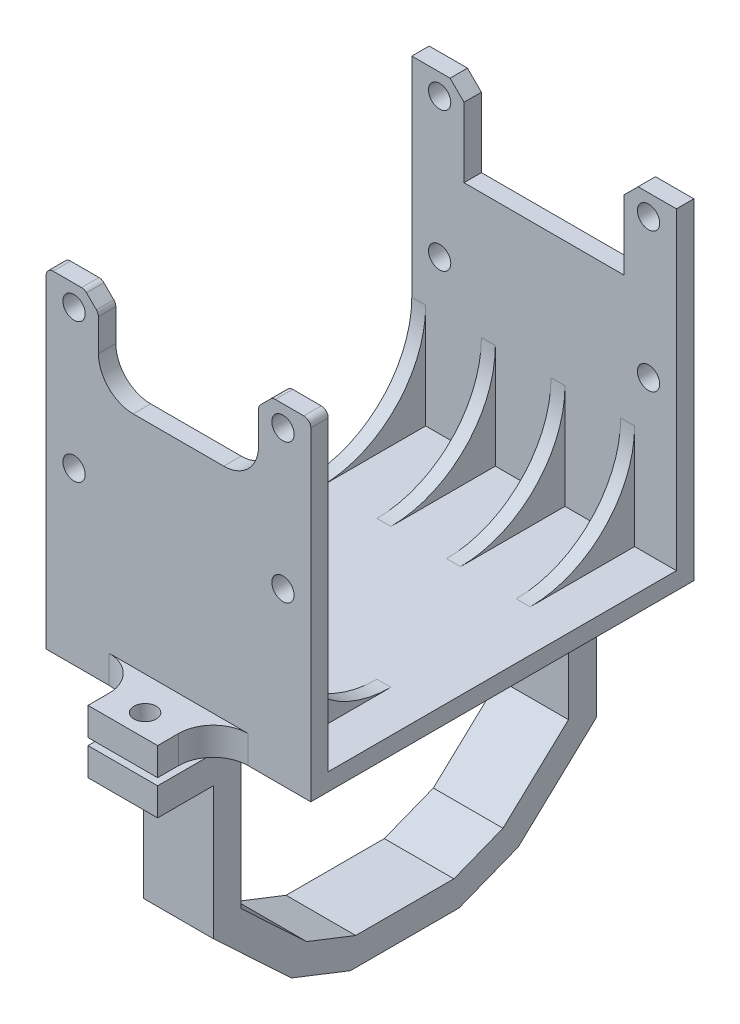
SolidWorks part; units mm, degrees
ref_plane "前视基准面" through (0, 0, 0) normal (0, 0, 1) x (1, 0, 0)
ref_plane "上视基准面" through (0, 0, 0) normal (0, 1, 0) x (1, 0, 0)
ref_plane "右视基准面" through (0, 0, 0) normal (1, 0, 0) x (0, 0, -1)
sketch "草图1" plane through (0, 0, 0) normal (0, 0, 1) x (1, 0, 0)
  line L1 (-19.3201, 24.1356) -> (18.6799, 24.1356)
  line L2 (-19.3201, 24.1356) -> (-19.3201, -20.8644)
  line L3 (-19.3201, -20.8644) -> (18.6799, -20.8644)
  line L4 (18.6799, 24.1356) -> (18.6799, -20.8644)
  circle A0 centre (-15.3201, 21.1356) radius 1.6
  circle A1 centre (14.6799, 21.1356) radius 1.6
  circle A2 centre (-15.3201, 1.1356) radius 1.6
  circle A3 centre (14.6799, 1.1356) radius 1.6
  dimension "D3" = 30
  dimension "D4" = 30
  dimension "D5" = 20
  dimension "D6" = 3.2
  dimension "D7" = 3.2
  dimension "D8" = 3.2
  dimension "D9" = 3.2
  dimension "D10" = 4
  dimension "D11" = 4
  dimension "D12" = 3
  dimension "D13" = 3
  dimension "D1" = 38
  dimension "D2" = 45
extrude "凸台-拉伸1" add sketch "草图1" along normal blind 2.5
sketch "草图2" plane through (0, 0, 2.5) normal (0, 0, 1) x (1, 0, 0)
  line L0 (18.6799, 24.1356) -> (-19.3201, 24.1356) construction
  line L1 (-11.8201, 24.1356) -> (11.1799, 24.1356)
  line L2 (-11.8201, 22.1356) -> (-11.8201, 12.1356)
  line L3 (-11.8201, 12.1356) -> (11.1799, 12.1356)
  line L4 (11.1799, 22.1356) -> (11.1799, 12.1356)
  line L5 (-13.8201, 24.1356) -> (-11.8201, 22.1356)
  line L6 (-11.8201, 24.1356) -> (-13.8201, 24.1356)
  line L7 (11.1799, 22.1356) -> (13.1799, 24.1356)
  line L8 (13.1799, 24.1356) -> (11.1799, 24.1356)
  circle A0 centre (-15.3201, 21.1356) radius 1.6 construction
  circle A1 centre (14.6799, 21.1356) radius 1.6 construction
  dimension "D2" = 3.5
  dimension "D1" = 3.5
  dimension "D3" = 12
  dimension "D4" = 2
  dimension "D5" = 2
  dimension "D6" = 2
  dimension "D7" = 2
extrude "切除-拉伸1" cut sketch "草图2" against normal blind 2.5
sketch "草图3" plane through (0, -20.8644, 0) normal (0, -1, 0) x (1, 0, 0)
  line L0 (18.6799, 2.5) -> (18.6799, 0) construction
  line L1 (-19.3201, 2.5) -> (18.6799, 2.5)
  line L2 (-19.3201, 2.5) -> (-19.3201, -52.5)
  line L3 (-19.3201, -52.5) -> (18.6799, -52.5)
  line L4 (18.6799, 2.5) -> (18.6799, -52.5)
  dimension "D1" = 55
extrude "凸台-拉伸2" add sketch "草图3" along normal blind 2.5
fillet "圆角3" radius 1 6 edges at (11.1799, 22.1356, 1.25) (13.1799, 24.1356, 1.25) (-19.3201, 24.1356, 1.25) (18.6799, 24.1356, 1.25) (-11.8201, 22.1356, 1.25) (-13.8201, 24.1356, 1.25)
fillet "Fillet1" radius 5 2 edges at (-11.8201, 12.1356, 1.25) (11.1799, 12.1356, 1.25)
sketch "Sketch4" plane through (-19.3201, 0, 0) normal (-1, 0, 0) x (0, 0, 1)
  line L0 (0, -5.8644) -> (0, -20.8644)
  line L1 (0, 23.1356) -> (0, -20.8644) construction
  line L2 (0, -20.8644) -> (-15, -20.8644)
  line L3 (0, -20.8644) -> (-52.5, -20.8644) construction
  arc A0 (0, -5.8644) -> (-15, -20.8644) centre (-15, -5.8644) cw
  dimension "D1" = 15
extrude "Extrude3" add sketch "Sketch4" against normal blind 2
ref_plane "Plane1" through (0, 0, -25) normal (0, 0, -1) x (-1, 0, 0)
mirror "Mirror1" about plane through (0, 0, -25) normal (0, 0, -1) of "凸台-拉伸1"
mirror "Mirror2" about plane through (0, 0, -25) normal (0, 0, -1) of "切除-拉伸1"
pattern_linear "LPattern1" count 4 spacing 10 along (1, 0, 0) of "Extrude3"
mirror "Mirror3" about plane through (0, 0, -25) normal (0, 0, -1) of "LPattern1"
ref_plane "Plane2" through (-0.3201, 0, 0) normal (-1, 0, 0) x (0, 0, 1)
sketch "Sketch5" plane through (-0.3201, 0, 0) normal (-1, 0, 0) x (0, 0, 1)
  line L0 (-48.5, -23.3644) -> (-48.5, -45.6488)
  line L1 (2.5, -23.3644) -> (-52.5, -23.3644) construction
  line L2 (-48.5, -45.6488) -> (-39.0953, -54.4416)
  line L3 (-39.0953, -54.4416) -> (-32.0493, -57.2068)
  line L4 (-32.0493, -57.2068) -> (-17.9507, -57.2068)
  line L5 (-25, -23.3644) -> (-25, -57.2068) construction
  line L6 (-7.5, -23.3644) -> (-42.5, -23.3644) construction
  line L7 (-48.5, -23.3644) -> (-52.5, -23.3644)
  line L8 (-52.5, -23.3644) -> (-52.5, -47.385)
  line L9 (-52.5, -47.385) -> (-41.2684, -57.8857)
  line L10 (-41.2684, -57.8857) -> (-32.8061, -61.2068)
  line L11 (-32.8061, -61.2068) -> (-17.1939, -61.2068)
  line L12 (-8.7316, -57.8857) -> (-17.1939, -61.2068)
  line L13 (2.5, -47.385) -> (-8.7316, -57.8857)
  line L14 (2.5, -28.3644) -> (2.5, -47.385)
  line L16 (-10.9047, -54.4416) -> (-17.9507, -57.2068)
  line L17 (-1.5, -45.6488) -> (-10.9047, -54.4416)
  line L18 (-1.5, -24.3644) -> (-1.5, -45.6488)
  line L19 (-1.5, -24.3644) -> (10.5, -24.3644)
  line L20 (10.5, -24.3644) -> (10.5, -28.3644)
  line L21 (10.5, -28.3644) -> (2.5, -28.3644)
  line L22 (2.5, -23.3644) -> (10.5, -23.3644)
  line L23 (10.5, -23.3644) -> (10.5, -19.3644)
  line L24 (10.5, -19.3644) -> (2.5, -19.3644)
  line L25 (2.5, 23.1356) -> (2.5, -23.3644) construction
  line L26 (2.5, -19.3644) -> (2.5, -23.3644)
  point P16 (-25, -57.2068)
  point P23 (-25, -61.2068)
  dimension "D1" = 4
  dimension "D2" = 4
  dimension "D3" = 4
  dimension "D4" = 4
  dimension "D5" = 22.2844
  dimension "D6" = 12.8749
  dimension "D7" = 133.074
  dimension "D8" = 7.5692
  dimension "D9" = 158.354
  dimension "D10" = 4
  dimension "D11" = 1
  dimension "D12" = 8
  dimension "D13" = 4
extrude "Extrude4" add sketch "Sketch5" along normal blind 5 and the other way blind 5
sketch "Sketch6" plane through (0, -28.3644, 0) normal (0, -1, 0) x (1, 0, 0)
  line L0 (4.6799, 10.5) -> (-5.3201, 10.5) construction
  circle A0 centre (-0.3201, 7.3) radius 1.6
  dimension "D1" = 3.2
  dimension "D2" = 3.2
extrude "Cut-Extrude1" cut sketch "Sketch6" against normal blind 20
fillet "Fillet2" radius 5 2 edges at (4.6799, -23.3644, -50.5) (-5.3201, -23.3644, -50.5)
fillet "Fillet3" radius 5 2 edges at (4.6799, -21.3644, 2.5) (-5.3201, -21.3644, 2.5)
